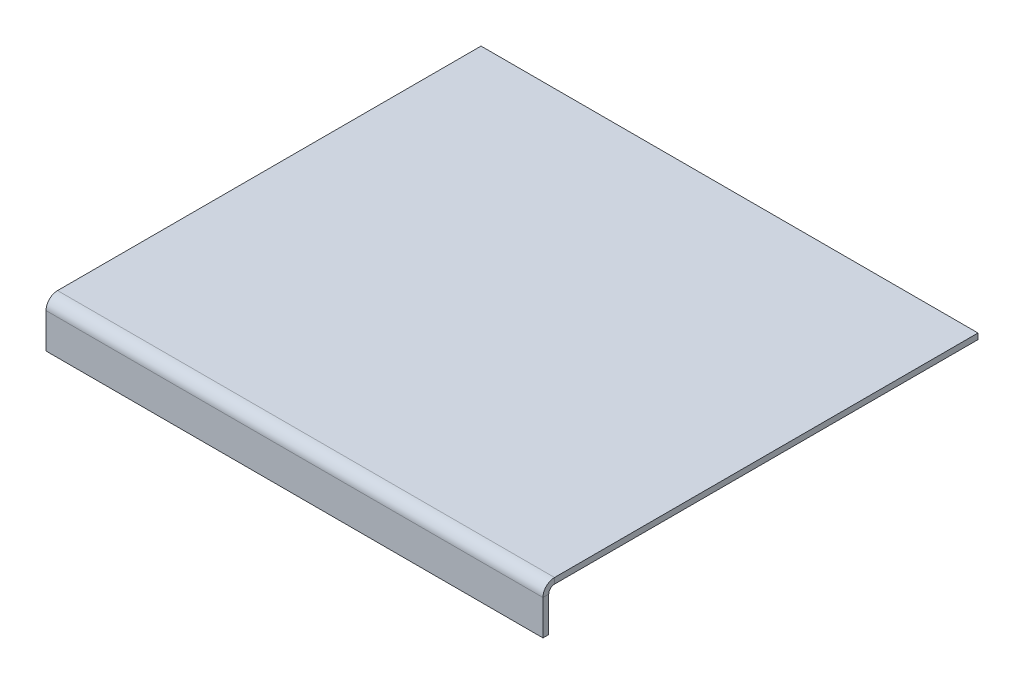
SolidWorks part; units mm, degrees
note: The reader was unsure of these and kept them because the rebuilt part matched: thickness of "Base-Flange1", "Edge-Flange4", "Sheet-Metal2", "Sheet-Metal6"; flange length of "Edge-Flange4".
ref_plane "Front Plane" through (0, 0, 0) normal (0, 0, 1) x (1, 0, 0)
ref_plane "Top Plane" through (0, 0, 0) normal (0, 1, 0) x (1, 0, 0)
ref_plane "Right Plane" through (0, 0, 0) normal (1, 0, 0) x (0, 0, -1)
sketch "Sketch1" plane through (0, 0, 0) normal (0, 1, 0) x (1, 0, 0)
  line L1 (101.6, -87.757) -> (-101.6, -87.757)
  line L2 (101.6, -87.757) -> (101.6, 87.757)
  line L3 (101.6, 87.757) -> (-101.6, 87.757)
  line L4 (-101.6, -87.757) -> (-101.6, 87.757)
  line L5 (101.6, -87.757) -> (-101.6, 87.757) construction
  line L6 (101.6, 87.757) -> (-101.6, -87.757) construction
  point P0 (0, 0)
  dimension "D1" = 203.2
  dimension "D2" = 175.514
base flange "Base-Flange1" sketch "Sketch1" thickness 2.3622 reverse thickness direction no parameters "D1"=10
edge flange "Edge-Flange4" sketch "Sketch35" flange angle 90 flange length 19.05 flange position material outside bend radius 2.36 thickness 2.3622 relief rectangular parameters "D6"=10
bend "EdgeBend9" bend radius 2.36 bend angle 90 parameters "D5"=1
sketch "Sketch35" plane through (0, -2.3622, 87.757) normal (0, 0, 1) x (-1, 0, 0)
  line L0 (101.6, 0) -> (-101.6, 0) construction
  line L1 (101.6, 0) -> (-101.6, 0)
  line L2 (-101.6, 0) -> (-101.6, 16.6878)
  line L3 (-101.6, 16.6878) -> (101.6, 16.6878)
  line L4 (101.6, 16.6878) -> (101.6, 0)
sketch "Bend-Lines1" [suppressed] plane through (0, 0, 0) normal (0, 1, 0) x (1, 0, 0)
sketch "Bounding-Box1" [suppressed] plane through (0, 0, 0) normal (0, 1, 0) x (1, 0, 0)
sheet metal parameters "Sheet-Metal2" thickness 2.3622 parameters "D1"=10
flat pattern "Flat-Pattern2" [suppressed]
sketch "Bend-Lines2" plane through (0, 0, 0) normal (0, 1, 0) x (1, 0, 0)
sketch3d "Bounding-Box2" [suppressed]
  line L0 (101.6, -88.9, 0) -> (-101.6, -88.9, 0) construction
  line L1 (101.6, 88.9, 0) -> (-101.6, 88.9, 0) construction
  line L2 (101.6, -88.9, 0) -> (101.6, 88.9, 0) construction
  line L3 (-101.6, -88.9, 0) -> (-101.6, 88.9, 0) construction
sheet metal parameters "Sheet-Metal6" thickness 2.3622 parameters "D1"=10
flat pattern "Flat-Pattern2"
sketch "Bend-Lines2" plane through (0, 0, 0) normal (0, 1, 0) x (1, 0, 0)
  line L0 (-101.6, -88.1782) -> (101.6, -88.1782) construction
  line L1 (-101.6, -88.1782) -> (101.6, -88.1782) construction
sketch3d "Bounding-Box2" [suppressed]
  line L0 (101.6, -105.2871, 0) -> (-101.6, -105.2871, 0) construction
  line L1 (101.6, 87.757, 0) -> (-101.6, 87.757, 0) construction
  line L2 (101.6, -105.2871, 0) -> (101.6, 87.757, 0) construction
  line L3 (-101.6, -105.2871, 0) -> (-101.6, 87.757, 0) construction
bend of the flat pattern "Flatten-<EdgeBend9>1"
